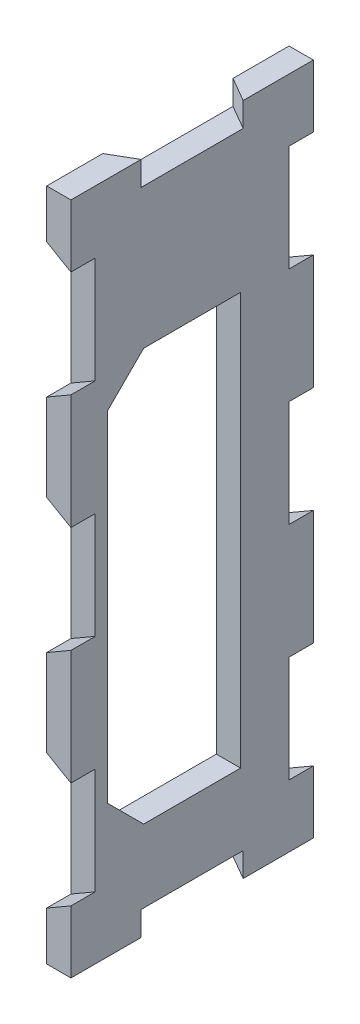
SolidWorks part; units mm, degrees
ref_plane "Front Plane" through (0, 0, 0) normal (1, 0, 0) x (0, 1, 0)
ref_plane "Top Plane" through (0, 0, 0) normal (0, 0, 1) x (0, 1, 0)
ref_plane "Right Plane" through (0, 0, 0) normal (0, 1, 0) x (-1, 0, 0)
sketch "Sketch2" plane through (0, 0, 0) normal (1, 0, 0) x (0, 1, 0)
  line L1 (-69.5, -25) -> (69.5, -25)
  line L2 (-69.5, -25) -> (-69.5, 25)
  line L3 (-69.5, 25) -> (69.5, 25)
  line L4 (69.5, -25) -> (69.5, 25)
  line L5 (-69.5, -25) -> (69.5, 25) construction
  line L6 (-69.5, 25) -> (69.5, -25) construction
  point P0 (0, 0)
  dimension "D1" = 139
  dimension "D2" = 50
extrude "Boss-Extrude1" add sketch "Sketch2" along normal blind 5
sketch "Sketch3" plane through (0, 0, -25) normal (0, 0, -1) x (1, 0, 0)
  line L0 (0, 31.7872) -> (0, 59.5)
  line L1 (0, 59.5) -> (24, 45.6436)
  line L2 (24, 45.6436) -> (0, 31.7872)
  line L3 (0, -27.5) -> (0, 27.5) construction
  line L4 (5, 69.5) -> (0, 69.5) construction
  line L5 (0, -13.8564) -> (0, 13.8564)
  line L6 (0, 13.8564) -> (24, 0)
  line L7 (24, 0) -> (0, -13.8564)
  line L8 (0, -59.5) -> (0, -31.7872)
  line L9 (0, -31.7872) -> (24, -45.6436)
  line L10 (24, -45.6436) -> (0, -59.5)
  line L11 (5, -69.5) -> (0, -69.5) construction
  circle A0 centre (8, 45.6436) radius 8
  dimension "D1" = 16
  dimension "D2" = 0
  dimension "D3" = 10
  dimension "D5" = 10
  dimension "D4" = 3
extrude "Cut-Extrude1" cut sketch "Sketch3" against normal blind 5 contours L7 L5 L6 | L9 L10 L8 | L2 L0 L1
extrude "Cut-Extrude2" cut sketch "Sketch3<3>" against normal blind 5 from offset 45 contours L7 L5 L6 | L9 L10 L8 | L2 L0 L1 offset against normal yes
sketch "Sketch3<3>" plane through (0, 0, -25) normal (0, 0, -1) x (1, 0, 0) same geometry as "Sketch3"
sketch "Sketch6" plane through (0, 69.5, 0) normal (0, 1, 0) x (-1, 0, 0)
  line L0 (0, 13.4234) -> (0, -13.4234)
  line L1 (0, -13.4234) -> (-23.25, 0)
  line L2 (0, 13.4234) -> (-23.25, 0)
  line L3 (0, 27.5) -> (0, -27.5) construction
  line L4 (-5, 25) -> (0, 25) construction
  circle A0 centre (-7.75, 0) radius 7.75
  dimension "D1" = 0
  dimension "D2" = 25
  dimension "D3" = 15.5
extrude "Cut-Extrude3" cut sketch "Sketch6" against normal blind 5 contours L1 L2 L0
extrude "Cut-Extrude5" cut sketch "Sketch6<3>" against normal blind 5 from offset 134 contours L1 L2 L0 offset against normal yes
sketch "Sketch6<3>" plane through (0, 69.5, 0) normal (0, 1, 0) x (-1, 0, 0) same geometry as "Sketch6"
sketch "Sketch4" plane through (0, 0, 0) normal (-1, 0, 0) x (0, -1, 0)
  line L0 (-35.5, -10) -> (49.5, -10)
  line L1 (49.5, -10) -> (49.5, 10)
  line L2 (49.5, 10) -> (42, 17.5)
  line L3 (42, 17.5) -> (-28, 17.5)
  line L4 (-28, 17.5) -> (-35.5, 10)
  line L5 (-35.5, 10) -> (-35.5, -10)
  line L7 (64.5, -13.4234) -> (64.5, 13.4234) construction
  line L8 (-64.5, -13.4234) -> (-64.5, 13.4234) construction
  line L9 (69.5, 25) -> (69.5, 13.4234) construction
  line L10 (31.7872, -20) -> (59.5, -20) construction
  dimension "D1" = 85
  dimension "D2" = 70
  dimension "D3" = 20
  dimension "D4" = 20
  dimension "D5" = 7.5
  dimension "D6" = 10
  dimension "D7" = 15
  dimension "D8" = 20
  dimension "D9" = 29
  dimension "D10" = 7.5
extrude "Cut-Extrude6" cut sketch "Sketch4" against normal blind 5 contours L0 L1 L2 L3 L4 L5
